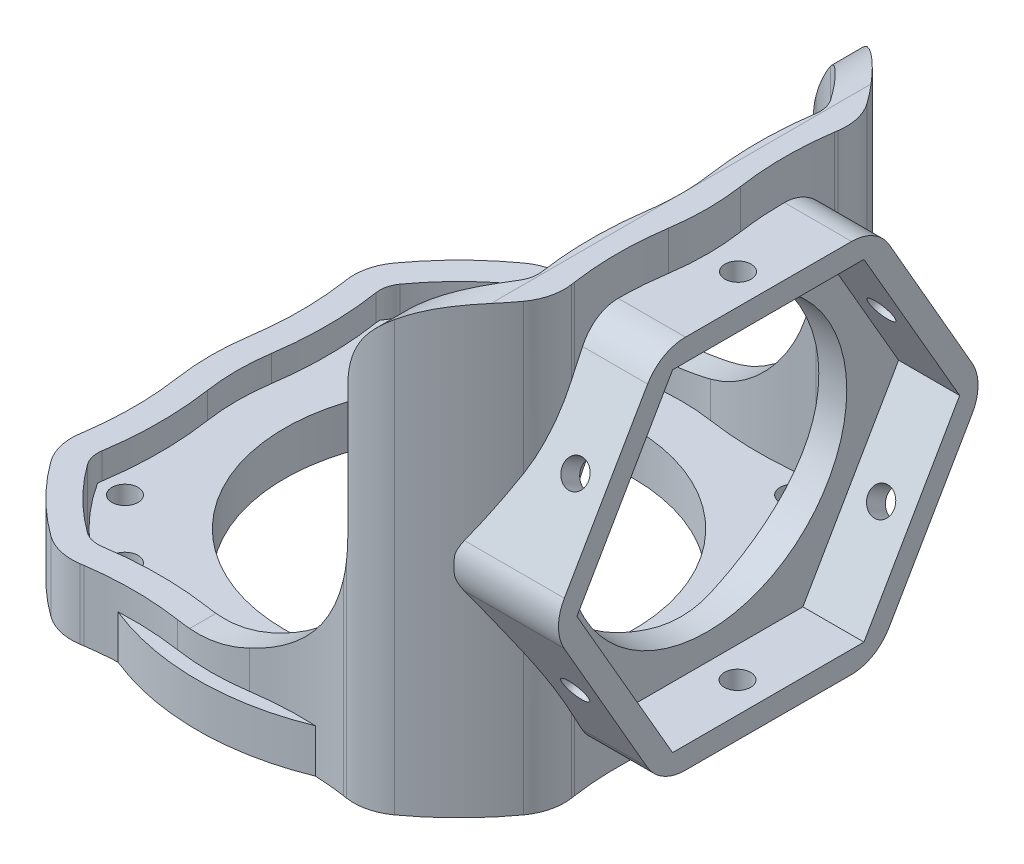
SolidWorks part; units mm, degrees
ref_plane "前视基准面" through (0, 0, 0) normal (0, 0, 1) x (1, 0, 0)
ref_plane "上视基准面" through (0, 0, 0) normal (0, 1, 0) x (1, 0, 0)
ref_plane "右视基准面" through (0, 0, 0) normal (1, 0, 0) x (0, 0, -1)
sketch "草图1" plane through (0, 0, 0) normal (0, 1, 0) x (1, 0, 0)
  line L0 (0, 0) -> (0, 46.6195) construction
  line L1 (0, 0) -> (-41.7463, 0) construction
  line L2 (-22.5267, 15.7734) -> (0, 0) construction
  line L3 (-15.7734, 22.5267) -> (0, 0) construction
  circle A0 centre (0, 0) radius 30
  circle A1 centre (0, 0) radius 20
  circle A2 centre (0, 0) radius 27.5 construction
  circle A3 centre (-22.5267, 15.7734) radius 1.5
  circle A4 centre (-15.7734, 22.5267) radius 1.5
  circle A5 centre (22.5267, 15.7734) radius 1.5
  circle A6 centre (15.7734, 22.5267) radius 1.5
  circle A7 centre (22.5267, -15.7734) radius 1.5
  circle A8 centre (15.7734, -22.5267) radius 1.5
  circle A9 centre (-22.5267, -15.7734) radius 1.5
  circle A10 centre (-15.7734, -22.5267) radius 1.5
  dimension "D1" = 60
  dimension "D2" = 40
  dimension "D3" = 55
  dimension "D5" = 3
  dimension "D4" = 35
  dimension "D6" = 35
extrude "凸台-拉伸1" add sketch "草图1" along normal blind 5
sketch "草图2" plane through (0, 5, 0) normal (0, 1, 0) x (1, 0, 0)
  line L0 (0, 0) -> (39.9587, 0) construction
  line L1 (0, 0) -> (0, -36.8515) construction
  line L2 (0, 0) -> (21.5668, 21.5668) construction
  arc A0 (24.7368, -3.2548) -> (24.949, 0.2177) centre (0, 0) ccw construction
  arc A1 (25.1774, -3.6784) -> (25.1774, 3.6784) centre (0.5, 0) ccw
  arc A2 (24.949, 0.2177) -> (24.6762, 3.686) centre (0, 0) ccw construction
  arc A3 (25.1774, 3.6784) -> (24.7671, 8.11) centre (64.7402, 9.5757) cw
  arc A4 (24.2388, 9.2464) -> (24.6762, 3.686) centre (64.2373, 9.5955) ccw construction
  arc A5 (24.7671, 8.11) -> (25.2125, 15.7044) centre (64.7402, 9.5757) cw
  arc A6 (24.7179, 15.7777) -> (24.2388, 9.2464) centre (64.2373, 9.5955) ccw construction
  arc A7 (25.2125, 15.7044) -> (24.675, 17.9275) centre (22.248, 16.1641) ccw
  arc A8 (24.7179, 15.7777) -> (24.2705, 17.6336) centre (22.248, 16.1641) ccw construction
  arc A9 (24.675, 17.9275) -> (17.9275, 24.675) centre (0, 0) ccw
  circle A10 centre (0, 0) radius 30 construction
  arc A11 (28.1446, 4.1207) -> (28.1446, -4.1207) centre (0.5, 0) cw
  arc A12 (28.1446, 4.1207) -> (28.1241, 14.8917) centre (64.7402, 9.5757) cw
  arc A13 (28.1241, 14.8917) -> (28.1806, 15.2677) centre (65.7457, 9.4297) cw
  arc A14 (28.1806, 15.2677) -> (27.1021, 19.6908) centre (22.248, 16.1641) ccw
  arc A15 (19.6908, 27.1021) -> (27.1021, 19.6908) centre (0, 0) cw
  arc A16 (15.2677, 28.1806) -> (19.6908, 27.1021) centre (16.1641, 22.248) cw
  arc A17 (14.8917, 28.1241) -> (15.2677, 28.1806) centre (9.4297, 65.7457) ccw
  arc A18 (4.1207, 28.1446) -> (14.8917, 28.1241) centre (9.5757, 64.7402) ccw
  arc A19 (4.1207, 28.1446) -> (-4.1207, 28.1446) centre (0, 0.5) ccw
  arc A20 (15.7044, 25.2125) -> (17.9275, 24.675) centre (16.1641, 22.248) cw
  arc A21 (8.11, 24.7671) -> (15.7044, 25.2125) centre (9.5757, 64.7402) ccw
  arc A22 (3.6784, 25.1774) -> (8.11, 24.7671) centre (9.5757, 64.7402) ccw
  arc A23 (-3.6784, 25.1774) -> (3.6784, 25.1774) centre (0, 0.5) cw
  arc A24 (-3.6784, 25.1774) -> (-8.11, 24.7671) centre (-9.5757, 64.7402) cw
  arc A25 (-8.11, 24.7671) -> (-15.7044, 25.2125) centre (-9.5757, 64.7402) cw
  arc A26 (-15.7044, 25.2125) -> (-17.9275, 24.675) centre (-16.1641, 22.248) ccw
  arc A27 (-4.1207, 28.1446) -> (-14.8917, 28.1241) centre (-9.5757, 64.7402) cw
  arc A28 (-14.8917, 28.1241) -> (-15.2677, 28.1806) centre (-9.4297, 65.7457) cw
  arc A29 (-15.2677, 28.1806) -> (-19.6908, 27.1021) centre (-16.1641, 22.248) ccw
  arc A30 (-19.6908, 27.1021) -> (-27.1021, 19.6908) centre (0, 0) ccw
  arc A31 (-28.1806, 15.2677) -> (-27.1021, 19.6908) centre (-22.248, 16.1641) cw
  arc A32 (-28.1241, 14.8917) -> (-28.1806, 15.2677) centre (-65.7457, 9.4297) ccw
  arc A33 (-28.1446, 4.1207) -> (-28.1241, 14.8917) centre (-64.7402, 9.5757) ccw
  arc A34 (-28.1446, 4.1207) -> (-28.1446, -4.1207) centre (-0.5, 0) ccw
  arc A35 (-24.675, 17.9275) -> (-17.9275, 24.675) centre (0, 0) cw
  arc A36 (-25.2125, 15.7044) -> (-24.675, 17.9275) centre (-22.248, 16.1641) cw
  arc A37 (-24.7671, 8.11) -> (-25.2125, 15.7044) centre (-64.7402, 9.5757) ccw
  arc A38 (-25.1774, 3.6784) -> (-24.7671, 8.11) centre (-64.7402, 9.5757) ccw
  arc A39 (-25.1774, -3.6784) -> (-25.1774, 3.6784) centre (-0.5, 0) cw
  arc A40 (-25.1774, -3.6784) -> (-24.7671, -8.11) centre (-64.7402, -9.5757) cw
  arc A41 (-24.7671, -8.11) -> (-25.2125, -15.7044) centre (-64.7402, -9.5757) cw
  arc A42 (-25.2125, -15.7044) -> (-24.675, -17.9275) centre (-22.248, -16.1641) ccw
  arc A43 (-24.675, -17.9275) -> (-17.9275, -24.675) centre (0, 0) ccw
  arc A44 (-28.1446, -4.1207) -> (-28.1241, -14.8917) centre (-64.7402, -9.5757) cw
  arc A45 (-28.1241, -14.8917) -> (-28.1806, -15.2677) centre (-65.7457, -9.4297) cw
  arc A46 (-28.1806, -15.2677) -> (-27.1021, -19.6908) centre (-22.248, -16.1641) ccw
  arc A47 (-19.6908, -27.1021) -> (-27.1021, -19.6908) centre (0, 0) cw
  arc A48 (-15.2677, -28.1806) -> (-19.6908, -27.1021) centre (-16.1641, -22.248) cw
  arc A49 (-14.8917, -28.1241) -> (-15.2677, -28.1806) centre (-9.4297, -65.7457) ccw
  arc A50 (-4.1207, -28.1446) -> (-14.8917, -28.1241) centre (-9.5757, -64.7402) ccw
  arc A51 (-15.7044, -25.2125) -> (-17.9275, -24.675) centre (-16.1641, -22.248) cw
  arc A52 (-8.11, -24.7671) -> (-15.7044, -25.2125) centre (-9.5757, -64.7402) ccw
  arc A53 (-3.6784, -25.1774) -> (-8.11, -24.7671) centre (-9.5757, -64.7402) ccw
  arc A54 (-3.6784, -25.1774) -> (3.6784, -25.1774) centre (0, -0.5) ccw
  arc A55 (3.6784, -25.1774) -> (8.11, -24.7671) centre (9.5757, -64.7402) cw
  arc A56 (8.11, -24.7671) -> (15.7044, -25.2125) centre (9.5757, -64.7402) cw
  arc A57 (15.7044, -25.2125) -> (17.9275, -24.675) centre (16.1641, -22.248) ccw
  arc A58 (4.1207, -28.1446) -> (-4.1207, -28.1446) centre (0, -0.5) cw
  arc A59 (4.1207, -28.1446) -> (14.8917, -28.1241) centre (9.5757, -64.7402) cw
  arc A60 (14.8917, -28.1241) -> (15.2677, -28.1806) centre (9.4297, -65.7457) cw
  arc A61 (15.2677, -28.1806) -> (19.6908, -27.1021) centre (16.1641, -22.248) ccw
  arc A62 (19.6908, -27.1021) -> (27.1021, -19.6908) centre (0, 0) ccw
  arc A63 (28.1806, -15.2677) -> (27.1021, -19.6908) centre (22.248, -16.1641) cw
  arc A64 (28.1241, -14.8917) -> (28.1806, -15.2677) centre (65.7457, -9.4297) ccw
  arc A65 (28.1446, -4.1207) -> (28.1241, -14.8917) centre (64.7402, -9.5757) ccw
  arc A66 (24.675, -17.9275) -> (17.9275, -24.675) centre (0, 0) cw
  arc A67 (25.2125, -15.7044) -> (24.675, -17.9275) centre (22.248, -16.1641) cw
  arc A68 (24.7671, -8.11) -> (25.2125, -15.7044) centre (64.7402, -9.5757) ccw
  arc A69 (25.1774, -3.6784) -> (24.7671, -8.11) centre (64.7402, -9.5757) ccw
  point P7 (24.95, 0)
  point P9 (25.45, 0)
  point P13 (0, -24.95)
  point P60 (0, 25.45)
  point P61 (0, 24.95)
  point P85 (-25.45, 0)
  point P86 (-24.95, 0)
  point P129 (0, -25.45)
  dimension "D2" = 30.5
  dimension "D1" = 0.5
extrude "凸台-拉伸2" add sketch "草图2" along normal blind 46 and the other way blind 5
sketch "草图3" plane through (0, 0, 0) normal (0, 0, 1) x (1, 0, 0)
  line L0 (-30.7273, 8) -> (-30.7273, -1.7514)
  line L2 (-30.7273, -1.7514) -> (-34.3096, -1.7514)
  line L3 (-34.3096, -1.7514) -> (-34.3096, 55.8818)
  line L4 (-34.3096, 55.8818) -> (36.2257, 55.8818)
  line L5 (36.2257, 55.8818) -> (36.2257, -1.7514)
  line L6 (36.2257, -1.7514) -> (28.45, -1.7514)
  line L7 (28.45, -1.7514) -> (28.45, 51)
  line L8 (28.45, 5) -> (28.45, 51) construction
  line L9 (28.45, 51) -> (25.45, 51)
  line L10 (14.8917, 51) -> (4.1207, 51) construction
  line L11 (15.45, 41) -> (15.45, 26)
  line L12 (-2.55, 8) -> (-30.7273, 8)
  line L13 (-27.7815, 5) -> (-30, 5) construction
  arc A0 (15.45, 26) -> (-2.55, 8) centre (-2.55, 26) cw
  arc A1 (25.45, 51) -> (15.45, 41) centre (25.45, 41) ccw
  point P20 (15.45, 51)
  dimension "D1" = 18
  dimension "D2" = 10
  dimension "D3" = 3
  dimension "D4" = 3
extrude "切除-拉伸1" cut sketch "草图3" along normal through all and the other way through all
sketch "草图4" plane through (28.45, 0, 0) normal (1, 0, 0) x (0, 0, -1)
  line L0 (0, 0) -> (0, 56.7093) construction
  line L1 (28.1446, 5) -> (27.7402, 5) construction
  circle A2 centre (0, 25) radius 20 construction
  circle A3 centre (0, 25) radius 16
  dimension "D1" = 40
  dimension "D2" = 32
extrude "切除-拉伸2" cut sketch "草图4" against normal blind 22 and the other way blind 19
sketch "草图5" plane through (28.45, 0, 0) normal (1, 0, 0) x (0, 0, -1)
  line L1 (13.8308, 5.9813) -> (23.3793, 22.4685)
  line L2 (23.386, 27.4685) -> (13.882, 43.9813)
  line L3 (9.5553, 46.4871) -> (-9.4973, 46.5128)
  line L4 (-13.8308, 44.0187) -> (-23.3793, 27.5315)
  line L5 (-23.386, 22.5315) -> (-13.882, 6.0187)
  line L6 (-9.5553, 3.5129) -> (9.4973, 3.4872)
  circle A0 centre (0, 25) radius 16
  arc A1 (-4.1207, 40.4603) -> (-14.8917, 30.8513) centre (0, 25) ccw construction
  circle A2 centre (0, 25) radius 22.5 construction
  circle A3 centre (0, 25) radius 21.5 construction
  arc A4 (13.882, 43.9813) -> (9.5553, 46.4871) centre (9.5485, 41.4871) ccw
  arc A5 (23.3793, 22.4685) -> (23.386, 27.4685) centre (19.0525, 24.9743) ccw
  arc A6 (13.8308, 5.9813) -> (9.4973, 3.4872) centre (9.504, 8.4872) cw
  arc A7 (-13.882, 6.0187) -> (-9.5553, 3.5129) centre (-9.5485, 8.5129) ccw
  arc A8 (-23.3793, 27.5315) -> (-23.386, 22.5315) centre (-19.0525, 25.0257) ccw
  arc A9 (-9.4973, 46.5128) -> (-13.8308, 44.0187) centre (-9.504, 41.5128) ccw
  dimension "D1" = 45
  dimension "D2" = 43
  dimension "D3" = 5
sketch "草图7" plane through (0, 51, 0) normal (0, 1, 0) x (1, 0, 0)
  line L0 (28.1241, -14.8917) -> (31.1027, -14.0835)
  line L1 (31.1027, -14.0835) -> (31.1027, 14.2516)
  line L2 (31.1027, 14.2516) -> (28.1241, 14.8917)
  arc A0 (28.1241, -14.8917) -> (28.1446, -4.1207) centre (64.7402, -9.5757) cw
  arc A1 (28.1446, -4.1207) -> (28.1241, -14.8917) centre (64.7402, -9.5757) ccw construction
  arc A2 (28.1446, -4.1207) -> (28.1446, 4.1207) centre (0.5, 0) ccw
  arc A3 (28.1446, 4.1207) -> (28.1241, 14.8917) centre (64.7402, 9.5757) cw
extrude "切除-拉伸3" cut sketch "草图7" against normal through all
extrude "凸台-拉伸4" add sketch "草图5" along normal blind 7 and the other way blind 5
sketch "草图8" plane through (0, 51, 0) normal (0, 1, 0) x (1, 0, 0)
  line L0 (17.9275, -24.675) -> (17.9275, 24.675)
  arc A0 (17.9275, -24.675) -> (24.675, -17.9275) centre (0, 0) ccw
  arc A1 (24.675, -17.9275) -> (25.2125, -15.7044) centre (22.248, -16.1641) ccw
  arc A2 (25.2125, -15.7044) -> (25.1774, -3.6784) centre (64.7402, -9.5757) cw
  arc A3 (25.1774, -3.6784) -> (25.45, 0) centre (0.5, 0) ccw
  arc A4 (25.45, 0) -> (25.1774, 3.6784) centre (0.5, 0) ccw
  arc A5 (25.1774, 3.6784) -> (25.2125, 15.7044) centre (64.7403, 9.5757) cw
  arc A6 (25.2125, 15.7044) -> (24.675, 17.9275) centre (22.248, 16.1641) ccw
  arc A7 (24.675, 17.9275) -> (17.9275, 24.675) centre (0, 0) ccw
extrude "切除-拉伸4" cut sketch "草图8" against normal up to surface (46 mm away) up to face at (0, 5, 28.5061)
sketch "草图9" plane through (35.45, 0, 0) normal (1, 0, 0) x (0, 0, -1)
  line L1 (10.9697, 6) -> (21.9393, 25)
  line L2 (21.9393, 25) -> (10.9697, 44)
  line L3 (10.9697, 44) -> (-10.9697, 44)
  line L4 (-10.9697, 44) -> (-21.9393, 25)
  line L5 (-21.9393, 25) -> (-10.9697, 6)
  line L6 (-10.9697, 6) -> (10.9697, 6)
  circle A2 centre (0, 25) radius 19 construction
  dimension "D2" = 38
extrude "切除-拉伸5" cut sketch "草图9" against normal blind 7
sketch "草图10" plane through (0, 17.0543, 29.4472) normal (0, 0.5012, 0.8654) x (1, 0, 0)
  line L0 (35.45, 21.6338) -> (31.95, 21.6338) construction
  line L1 (35.45, 31.16) -> (35.45, 12.1075) construction
  circle A0 centre (31.95, 21.6338) radius 1.5
  circle A1 centre (31.95, 21.6338) radius 3 construction
  dimension "D2" = 3
  dimension "D3" = 6
  dimension "D1" = 3.5
sketch "草图11" plane through (0, -4.5041, 7.8256) normal (0, -0.4988, 0.8667) x (1, 0, 0)
  line L0 (35.45, 21.6675) -> (31.95, 21.6675) construction
  line L1 (35.45, 31.1937) -> (35.45, 12.1412) construction
  circle A0 centre (31.95, 21.6675) radius 1.5
  circle A1 centre (31.95, 21.6675) radius 3 construction
  dimension "D1" = 6
  dimension "D2" = 3
  dimension "D3" = 3.5
extrude "切除-拉伸6" cut sketch "草图10" against normal through all
extrude "切除-拉伸7" cut sketch "草图11" against normal through all
sketch "草图12" plane through (0, 3.5, -0.0047) normal (0, -1, 0.0013) x (1, 0, 0)
  line L0 (35.45, 0.0337) -> (31.95, 0.0337) construction
  line L1 (35.45, 9.56) -> (35.45, -9.4926) construction
  circle A0 centre (31.95, 0.0337) radius 1.5
  circle A1 centre (31.95, 0.0337) radius 3 construction
  dimension "D2" = 3
  dimension "D3" = 6
  dimension "D1" = 3.5
extrude "切除-拉伸8" cut sketch "草图12" against normal through all
